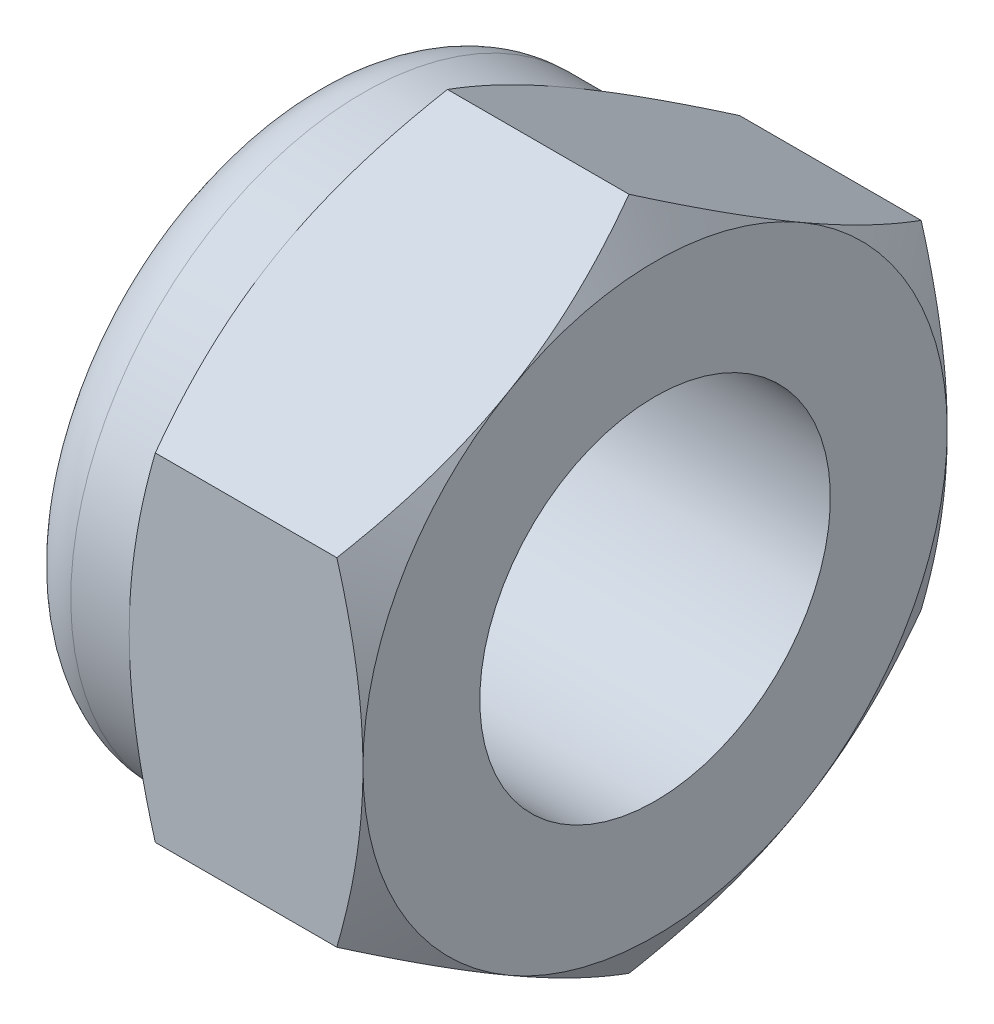
SolidWorks part; units mm, degrees
material "AISI 1020"
ref_plane "XY (Front)" through (0, 0, 0) normal (0, 0, 1) x (1, 0, 0)
ref_plane "XZ (Top)" through (0, 0, 0) normal (0, 1, 0) x (1, 0, 0)
ref_plane "YZ (Right)" through (0, 0, 0) normal (1, 0, 0) x (0, 0, -1)
ref_axis "X" through (-88.99, 0, 0) along (1, 0, 0)
ref_axis "Y" through (0, 55, 0) along (0, -1, 0)
ref_axis "Z" through (0, 0, -88.99) along (0, 0, 1)
sketch "Sketch1" plane through (0, 0, 0) normal (1, 0, 0) x (0, 0, -1)
  line L1 (0, 5.7735) -> (-5, 2.8868)
  line L2 (-5, 2.8868) -> (-5, -2.8868)
  line L3 (-5, -2.8868) -> (0, -5.7735)
  line L4 (0, -5.7735) -> (5, -2.8868)
  line L5 (5, -2.8868) -> (5, 2.8868)
  line L6 (5, 2.8868) -> (0, 5.7735)
  circle A0 centre (0, 0) radius 5 construction
  dimension "s" = 10
extrude "Boss-Extrude1" add sketch "Sketch1" against normal blind 6
sketch "Sketch2" plane through (0, 0, 0) normal (0, 0, 1) x (1, 0, 0)
  line L0 (-8.122, 0) -> (-6, 0) construction
  line L1 (-6, 2.8868) -> (-6, -2.8868) construction
  line L2 (0, 5) -> (-0.4466, 5.7735)
  line L3 (0, 5.7735) -> (0, 2.8868) construction
  line L4 (-6, 5.7735) -> (0, 5.7735) construction
  line L5 (-0.4466, 5.7735) -> (0, 5.7735)
  line L6 (0, 5.7735) -> (0, 5)
  line L7 (0, -5) -> (0, 5) construction
  line L8 (-6, 5.7735) -> (-6, 2.8868) construction
  line L9 (-3.5534, 5.7735) -> (-4, 5)
  line L10 (-6, 0) -> (-6, 3)
  line L12 (-4, 5) -> (-5, 5)
  line L13 (-6, 4) -> (-6.7735, 4)
  line L14 (-6, 3) -> (0, 3)
  line L15 (0, 2.8868) -> (0, -2.8868) construction
  line L16 (0, 3) -> (0, 0)
  line L17 (0, 0) -> (-6, 0)
  line L18 (-6.7735, 4) -> (-6.7735, 5.7735)
  line L20 (-6.7735, 5.7735) -> (-3.5534, 5.7735)
  line L21 (-4, 5) -> (0, 5) construction
  line L22 (-4, 5) -> (-4, 5.7735) construction
  line L23 (-2, 5) -> (-2, 5.7735) construction
  arc A0 (-5, 5) -> (-6, 4) centre (-5, 4) ccw
  dimension "D1" = 30
  dimension "R" = 1
  dimension "m" = 4
  dimension "M_t" = 6
revolve "Cut-Revolve4" cut sketch "Sketch2" angle 360 about L0
